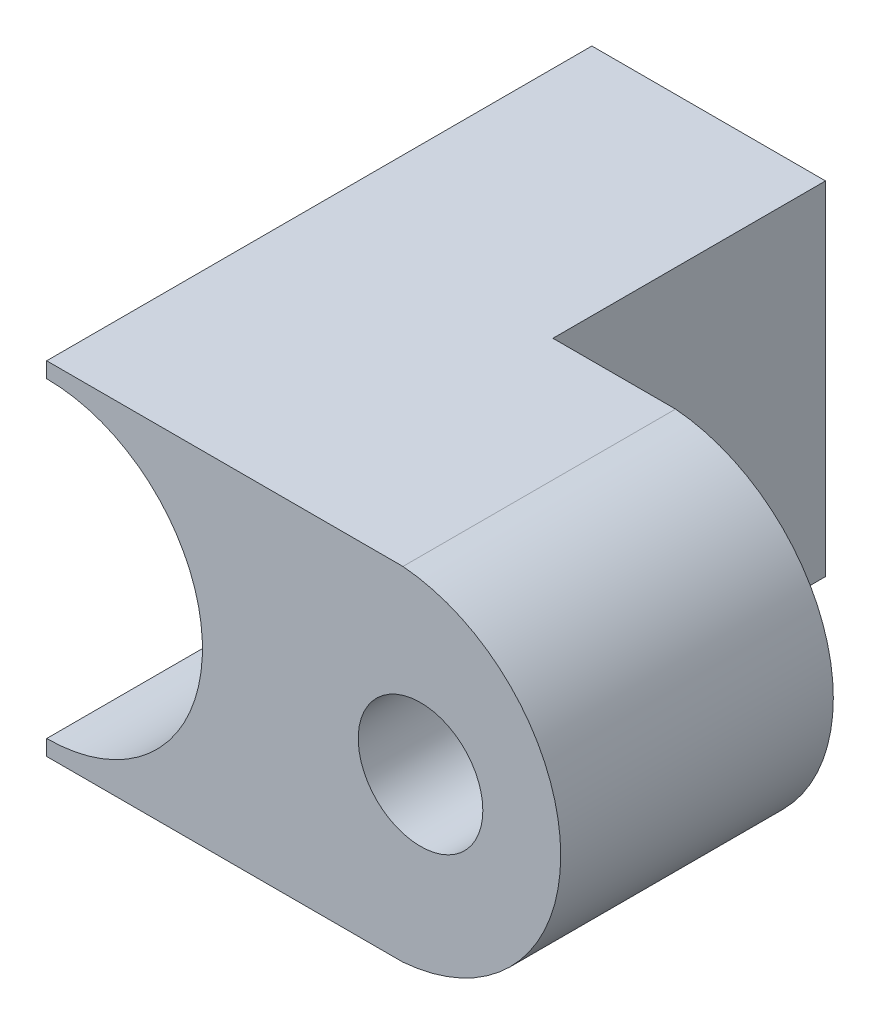
SolidWorks part; units mm, degrees
material "AISI Type A2 Tool Steel Custom"
ref_plane "Front Plane" through (0, 0, 0) normal (0, 0, 1) x (1, 0, 0)
ref_plane "Top Plane" through (0, 0, 0) normal (0, 1, 0) x (1, 0, 0)
ref_plane "Right Plane" through (0, 0, 0) normal (1, 0, 0) x (0, 0, -1)
sketch "Sketch1" plane through (0, 0, 0) normal (0, 0, 1) x (1, 0, 0)
  line L1 (0, -1.27) -> (29.0467, -1.27)
  line L3 (0, 26.67) -> (29.0467, 26.67)
  line L9 (0, 25.4) -> (0, 26.67)
  line L10 (0, 0) -> (0, -1.27)
  arc A1 (0, 0) -> (0, 25.4) centre (0, 12.7) ccw
  arc A4 (29.0467, -1.27) -> (29.0467, 26.67) centre (27.8924, 12.7) ccw
  point P3 (41.91, 12.7)
  dimension "D2" = 25.4
  dimension "D5" = 14.0176
  dimension "D3" = 41.91
  dimension "D1" = 1.27
  dimension "D4" = 1.27
extrude "Boss-Extrude1" add sketch "Sketch1" along normal blind 44.45
sketch "Sketch2" plane through (0, 0, 0) normal (0, 0, -1) x (-1, 0, 0)
  line L0 (-19.05, -1.27) -> (-19.05, 26.67)
  line L1 (0, -1.27) -> (-29.0467, -1.27) construction
  line L2 (-29.0467, 26.67) -> (0, 26.67) construction
  line L3 (0, -1.27) -> (-29.0467, -1.27) construction
  line L4 (-29.0467, 26.67) -> (0, 26.67) construction
  line L5 (-19.05, -1.27) -> (-29.0467, -1.27)
  line L10 (-29.0467, 26.67) -> (-19.05, 26.67)
  arc A1 (-29.0467, 26.67) -> (-29.0467, -1.27) centre (-27.8924, 12.7) ccw construction
  arc A3 (-29.0467, 26.67) -> (-29.0467, -1.27) centre (-27.8924, 12.7) ccw
  dimension "D1" = 19.05
extrude "Cut-Extrude1" cut sketch "Sketch2" against normal blind 22.225
sketch "Sketch3" plane through (0, 0, 44.45) normal (0, 0, 1) x (1, 0, 0)
  arc A0 (29.0467, -1.27) -> (29.0467, 26.67) centre (27.8924, 12.7) ccw construction
  point P0 (30.48, 12.7)
  point P13 (41.91, 12.7)
  dimension "D2" = 11.43
hole_wizard "3/8 (0.375) Diameter Hole1" positions "Sketch3" profile "Sketch4" hole size "3/8" standard "ANSI Inch" end condition through all
sketch "Sketch4" plane through (30.48, 12.7, 44.45) normal (1, 0, 0) x (0, -1, 0)
  line L0 (0, 0) -> (0, 44.45)
  line L1 (0, 44.45) -> (5.08, 44.45)
  line L2 (5.08, 44.45) -> (5.08, 0)
  line L5 (5.08, 0) -> (0, 0)
  line L11 (0, -6.35) -> (0, 107.95) construction
  dimension "Thru Hole Dia." = 10.16
  dimension "Thru Hole Depth" = 44.45
